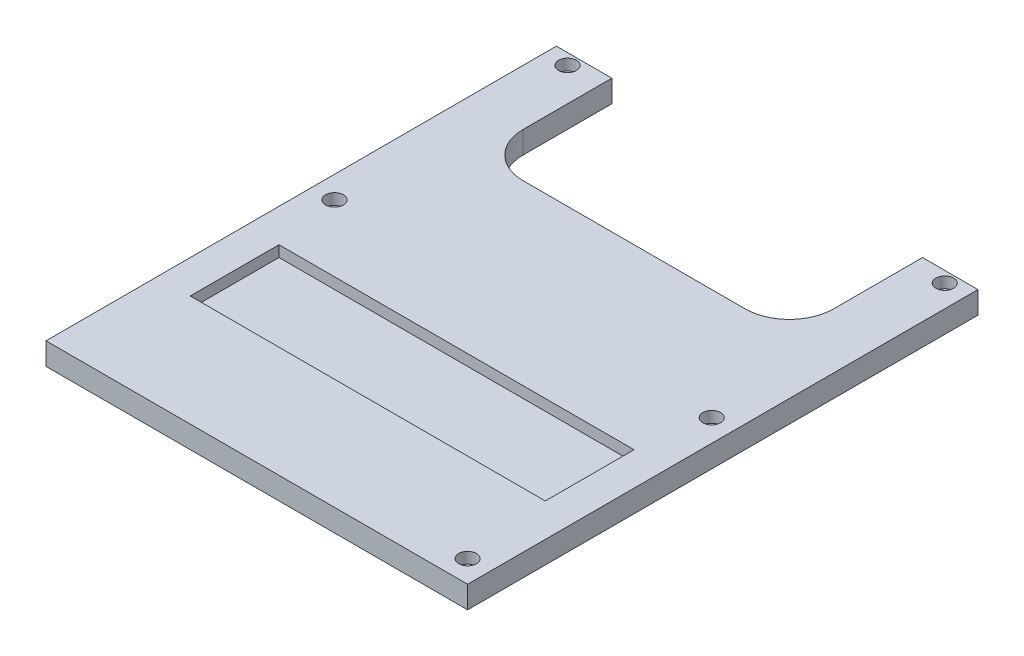
SolidWorks part; units mm, degrees
material "ABS"
ref_plane "Front" through (0, 0, 0) normal (0, 0, 1) x (1, 0, 0)
ref_plane "Top" through (0, 0, 0) normal (0, 1, 0) x (1, 0, 0)
ref_plane "Right" through (0, 0, 0) normal (1, 0, 0) x (0, 0, -1)
sketch "Sketch1" plane through (0, 0, 0) normal (0, 1, 0) x (1, 0, 0)
  line L1 (-60.325, 73.025) -> (60.325, 73.025)
  line L2 (-60.325, 73.025) -> (-60.325, -73.025)
  line L3 (-60.325, -73.025) -> (60.325, -73.025)
  line L4 (60.325, 73.025) -> (60.325, -73.025)
  line L5 (-60.325, 73.025) -> (60.325, -73.025) construction
  line L6 (-60.325, -73.025) -> (60.325, 73.025) construction
  point P0 (0, 0)
  dimension "D1" = 120.65
  dimension "D2" = 146.05
extrude "Boss-Extrude1" add sketch "Sketch1" along normal blind 6.35
sketch "Sketch7" plane through (0, 6.35, 0) normal (0, 1, 0) x (1, 0, 0)
  line L1 (-60.325, 73.025) -> (-60.325, -73.025) construction
  line L2 (60.325, -73.025) -> (60.325, 73.025) construction
  line L3 (-60.325, -73.025) -> (60.325, -73.025) construction
  circle A0 centre (-53.975, 3.175) radius 2.54
  circle A1 centre (53.975, 3.175) radius 2.54
  circle A2 centre (53.975, -66.675) radius 2.54
  circle A3 centre (-53.975, 69.85) radius 2.54
  circle A4 centre (53.975, 69.85) radius 2.54
  dimension "D5" = 5.08
  dimension "D1" = 76.2
  dimension "D2" = 6.35
  dimension "D3" = 6.35
  dimension "D4" = 6.35
  dimension "D6" = 66.675
extrude "Cut-Extrude1" cut sketch "Sketch7" against normal offset from surface (3.175 mm away) 3.175 up to face at (0, 0, 0)
hole_wizard "#2 Clearance Hole2" positions "Sketch8" profile "Sketch10" hole size "#2" standard "ANSI Inch" end condition through all
sketch "Sketch8" plane through (0, 3.175, 0) normal (0, 1, 0) x (1, 0, 0)
  point P0 (-53.975, 3.175)
  point P3 (53.975, 3.175)
  point P6 (53.975, -66.675)
  point P9 (-53.975, 69.85)
  point P12 (53.975, 69.85)
sketch "Sketch10" plane through (-53.975, 3.175, -3.175) normal (1, 0, 0) x (0, 0, 1)
  line L0 (0, 0) -> (0, 3.175)
  line L1 (0, 3.175) -> (1.0795, 3.175)
  line L2 (1.0795, 3.175) -> (1.0795, 0.8275)
  line L3 (1.0795, 0.8275) -> (1.7145, 0)
  line L5 (1.7145, 0) -> (0, 0)
  line L6 (-1.0795, 0.8275) -> (-1.7145, 0) construction
  line L11 (0, -6.35) -> (0, 107.95) construction
  dimension "Thru Hole Dia." = 2.159
  dimension "Thru Hole Depth" = 3.175
  dimension "Near C'Sink Dia." = 3.429
  dimension "Near C'Sink Angle" = 75
sketch "Sketch13" plane through (0, 6.35, 0) normal (0, 1, 0) x (1, 0, 0)
  line L0 (60.325, 73.025) -> (-60.325, 73.025) construction
  line L1 (-44.45, 73.025) -> (44.45, 73.025)
  line L2 (-44.45, 73.025) -> (-44.45, 34.925)
  line L3 (-44.45, 34.925) -> (44.45, 34.925)
  line L4 (44.45, 73.025) -> (44.45, 34.925)
  line L5 (-44.45, 73.025) -> (44.45, 34.925) construction
  line L6 (-44.45, 34.925) -> (44.45, 73.025) construction
  point P0 (0, 53.975)
  dimension "D1" = 88.9
  dimension "D2" = 38.1
extrude "Cut-Extrude3" cut sketch "Sketch13" against normal through all
fillet "Fillet1" radius 12.7 2 edges at (44.45, 3.175, -34.925) (-44.45, 3.175, -34.925)
sketch "Sketch11" plane through (0, 6.35, 0) normal (0, 1, 0) x (1, 0, 0)
  line L0 (-60.325, -73.025) -> (60.325, -73.025) construction
  line L1 (-50.8, -15.875) -> (50.8, -15.875)
  line L2 (-50.8, -15.875) -> (-50.8, -41.275)
  line L3 (-50.8, -41.275) -> (50.8, -41.275)
  line L4 (50.8, -15.875) -> (50.8, -41.275)
  line L5 (-50.8, -15.875) -> (50.8, -41.275) construction
  line L6 (-50.8, -41.275) -> (50.8, -15.875) construction
  point P0 (0, -28.575)
  dimension "D1" = 25.4
  dimension "D2" = 101.6
  dimension "D3" = 44.45
extrude "Cut-Extrude2" cut sketch "Sketch11" against normal blind 3.175
